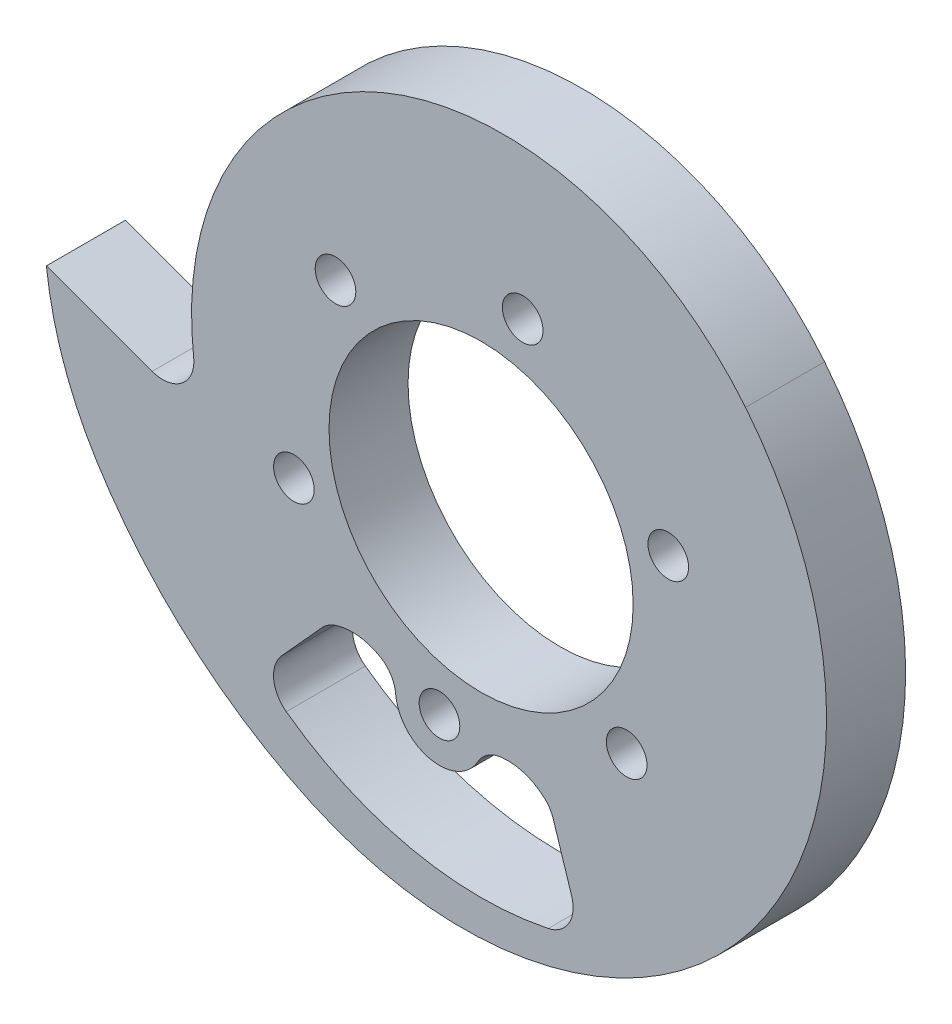
SolidWorks part; units mm, degrees
material "AR500 Weight at A2 Tool Steel Prop."
ref_plane "Front Plane" through (0, 0, 0) normal (0, 0, 1) x (1, 0, 0)
ref_plane "Top Plane" through (0, 0, 0) normal (0, 1, 0) x (1, 0, 0)
ref_plane "Right Plane" through (0, 0, 0) normal (1, 0, 0) x (0, 0, -1)
other "Center of Mass"
sketch "Sketch1" plane through (0, 0, 0) normal (0, 0, 1) x (1, 0, 0)
  line L0 (-69.85, 0) -> (-44.4783, -9.2345)
  line L1 (0, 0) -> (-61.8777, -22.9731) construction
  line L2 (-44.4783, -9.2345) -> (0, 0) construction
  line L3 (-27.2394, -53.4604) -> (0, 0) construction
  line L4 (42.4942, 36.4725) -> (0, 0) construction
  line L5 (0, 0) -> (-25.1554, 0) construction
  line L7 (-69.85, 0) -> (-69.5019, -2.1981) construction
  line L8 (-69.85, 0) -> (-69.85, 19.8503) construction
  line L9 (42.4942, 36.4725) -> (53.0039, 45.4929) construction
  circle A0 centre (0, 0) radius 69.85 construction
  circle A1 centre (0, 0) radius 44.45 construction
  circle A3 centre (0, 0) radius 21.4376 construction
  arc A4 (-69.85, 0) -> (-61.8777, -22.9731) centre (-15.0447, 6.1491) ccw
  arc A6 (-27.2394, -53.4604) -> (42.4942, 36.4725) centre (-2.927, -0.3101) ccw
  arc A8 (-44.4783, -9.2345) -> (42.4942, 36.4725) centre (3.5652, 4.9473) cw
  arc A9 (-61.8777, -22.9731) -> (-27.2394, -53.4604) centre (6.0192, 19.2474) ccw
  circle A10 centre (0, 0) radius 24.4376
  point P21 (-69.0678, -4.9384)
  dimension "D1" = 139.7
  dimension "D2" = 25.4
  dimension "D3" = 20
  dimension "D4" = 42.8752
  dimension "D5" = 27
  dimension "D6" = 25.3717
  dimension "D15" = 13.85
  dimension "D12" = 63
  dimension "D17" = 3
  dimension "D7" = 66.0046
  dimension "D8" = 45.4268
  dimension "D9" = 24.3171
  dimension "D10" = 9
  dimension "D11" = 5
  dimension "D13" = 60
  dimension "D14" = 56
  dimension "D16" = 40.639
extrude "Boss-Extrude1" add sketch "Sketch1" along normal mid plane 12.7 contours A1 | A1 A3 | A1 | A4 A9 A6 A8 L0 A10 region at (-57.7432, -6.2083, 0)
fillet "Fillet3" radius 5 1 edges at (-44.4783, -9.2345, 0)
other "Center of Mass Reference Point1"
sketch "Sketch5" plane through (0, 0, 6.35) normal (0, 0, 1) x (1, 0, 0)
  line L0 (0.2837, 1.3097) -> (1.2994, 5.9996) construction
  circle A0 centre (0, 0) radius 24.4376 construction
  circle A1 centre (0, 0) radius 24.4376 construction
  point P0 (-6.6861, -30.8719)
  point P1 (0, 0)
  point P3 (-5.1727, -23.8839)
  point P5 (-30.0789, -9.6456)
  point P6 (-23.3928, 21.2263)
  point P7 (6.6861, 30.8719)
  point P8 (30.0789, 9.6456)
  point P9 (23.3928, -21.2263)
  point P10 (0, 0)
  point P11 (-0.8966, -4.1399)
  point P19 (-5.1727, -23.8839)
  dimension "D1" = 7.15
  dimension "D2" = 6
hole_wizard "1/4 Clearance Hole1" positions "Sketch6" profile "Sketch8" hole size "1/4" standard "ANSI Inch" end condition through all
sketch "Sketch6" plane through (0, 0, 6.35) normal (0, 0, 1) x (1, 0, 0)
  point P0 (-6.6861, -30.8719)
  point P3 (-30.0789, -9.6456)
  point P6 (-23.3928, 21.2263)
  point P9 (6.6861, 30.8719)
  point P12 (30.0789, 9.6456)
  point P15 (23.3928, -21.2263)
sketch "Sketch8" plane through (-6.6861, -30.8719, 6.35) normal (1, 0, 0) x (0, -1, 0)
  line L0 (0, 0) -> (0, 12.7)
  line L1 (0, 12.7) -> (3.2639, 12.7)
  line L2 (3.2639, 12.7) -> (3.2639, 0)
  line L5 (3.2639, 0) -> (0, 0)
  line L11 (0, -6.35) -> (0, 107.95) construction
  dimension "Thru Hole Dia." = 6.5278
  dimension "Thru Hole Depth" = 12.7
sketch "Sketch9" plane through (0, 0, 6.35) normal (0, 0, 1) x (1, 0, 0)
  line L0 (-24.8451, -27.4155) -> (-35.5894, -39.2713)
  line L1 (16.152, 74.5785) -> (-13.5514, -62.5708) construction
  line L3 (16.152, -50.4773) -> (11.2758, -35.2384)
  line L4 (-24.8451, -27.4155) -> (0, 0) construction
  line L5 (6.6861, 30.8719) -> (8.1835, 37.7855) construction
  line L6 (-13.6833, -29.8329) -> (-24.8451, -27.4155) construction
  arc A1 (-35.5894, -39.2713) -> (16.152, -50.4773) centre (0, 0) ccw
  circle A2 centre (-6.6861, -30.8719) radius 3.2639 construction
  circle A3 centre (-6.6861, -30.8719) radius 3.2639 construction
  circle A4 centre (6.6861, 30.8719) radius 3.2639 construction
  circle A5 centre (0, 0) radius 24.4376 construction
  circle A6 centre (0, 0) radius 24.4376 construction
  circle A7 centre (-6.6861, -30.8719) radius 7.0739 construction
  arc A8 (-13.6833, -29.8329) -> (0.1139, -32.821) centre (-6.6861, -30.8719) ccw
  arc A9 (-13.6833, -29.8329) -> (-24.8451, -27.4155) centre (-20.6822, -35.1715) ccw
  arc A10 (0.1139, -32.821) -> (11.2758, -35.2384) centre (4.2769, -40.577) cw
  arc A11 (-27.2394, -53.4604) -> (42.4942, 36.4725) centre (-2.927, -0.3101) ccw construction
  arc A12 (-27.2394, -53.4604) -> (42.4942, 36.4725) centre (-2.927, -0.3101) ccw construction
  point P19 (-26.526, -29.3291)
  point P21 (-0.8966, -4.1399)
  point P27 (-20.5116, -37.2307)
  point P28 (-13.5514, -33.0385)
  point P29 (-26.18, -30.8719)
  point P33 (0, 0)
  point P34 (9.8635, -53.4604)
  point P35 (16.152, -50.4773)
  dimension "D1" = 3.81
  dimension "16" = 16
extrude "Cut-Extrude1" cut sketch "Sketch9" against normal through all
fillet "Fillet4" radius 5 6 edges at (16.152, -50.4773, 0) (-35.5894, -39.2713, 0) (11.2758, -35.2384, 0) (-24.8451, -27.4155, 0) (-13.6833, -29.8329, 0) (0.1139, -32.821, 0)
other "Center of Mass Reference Point2"
sketch "Sketch11" [suppressed] plane through (0, 0, 6.35) normal (0, 0, 1) x (1, 0, 0)
  line L0 (0, 0) -> (0.0077, 0.0102) construction
  line L1 (-0.8966, -4.1399) -> (0.0077, 0.0102) construction
  point P3 (0.3453, -5.4451)
  point P4 (0.3453, -2.3363)
  point P5 (0, 0)
  point P8 (0, 0)
  dimension "D1" = 0.0077
  dimension "D2" = 0.0102
  dimension "D3" = 0.0128
sketch "Sketch13" plane through (0, 0, 6.35) normal (0, 0, 1) x (1, 0, 0)
  line L0 (0, 0) -> (0.0112, 0.0518) construction
  point P3 (-0.9193, -4.2447)
  dimension "D1" = 0.053
